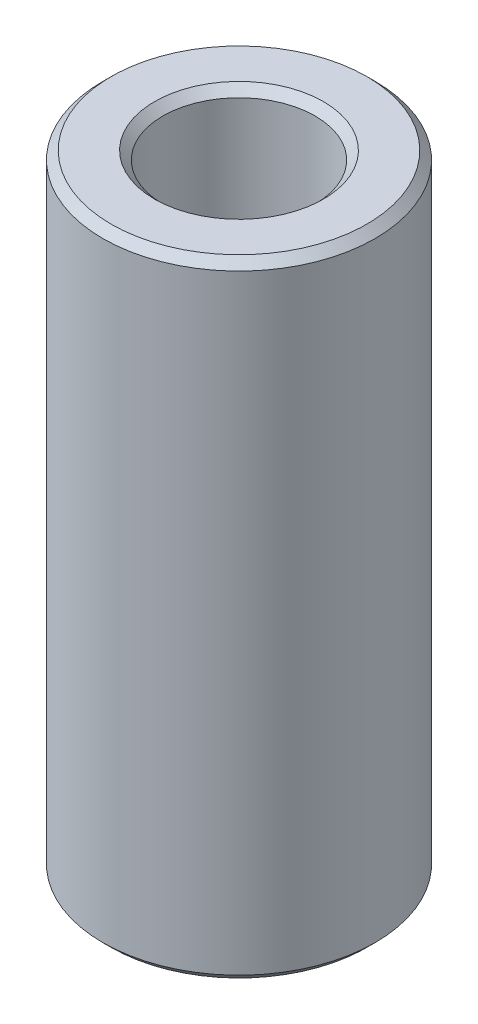
SolidWorks part; units mm, degrees
ref_plane "Front Plane" through (0, 0, 0) normal (0, 0, 1) x (1, 0, 0)
ref_plane "Top Plane" through (0, 0, 0) normal (0, 1, 0) x (1, 0, 0)
ref_plane "Right Plane" through (0, 0, 0) normal (1, 0, 0) x (0, 0, -1)
sketch "Sketch1" plane through (0, 0, 0) normal (0, 1, 0) x (1, 0, 0)
  circle A0 centre (0, 0) radius 45
  dimension "SLEEVE_OD" = 90
extrude "Boss-Extrude1" add sketch "Sketch1" along normal blind 207.0149
sketch "Sketch2" plane through (0, 0, 0) normal (0, 1, 0) x (1, 0, 0)
  circle A0 centre (0, 0) radius 25.1768
  dimension "BORE_D" = 50.3536
extrude "Cut-Extrude1" cut sketch "Sketch2" along normal through all
chamfer "Chamfer1" distance 2.7434 angle 45 4 edges at (0, 207.0149, 25.1768) (0, 0, 25.1768) (0, 0, 45) (0, 207.0149, 45)
